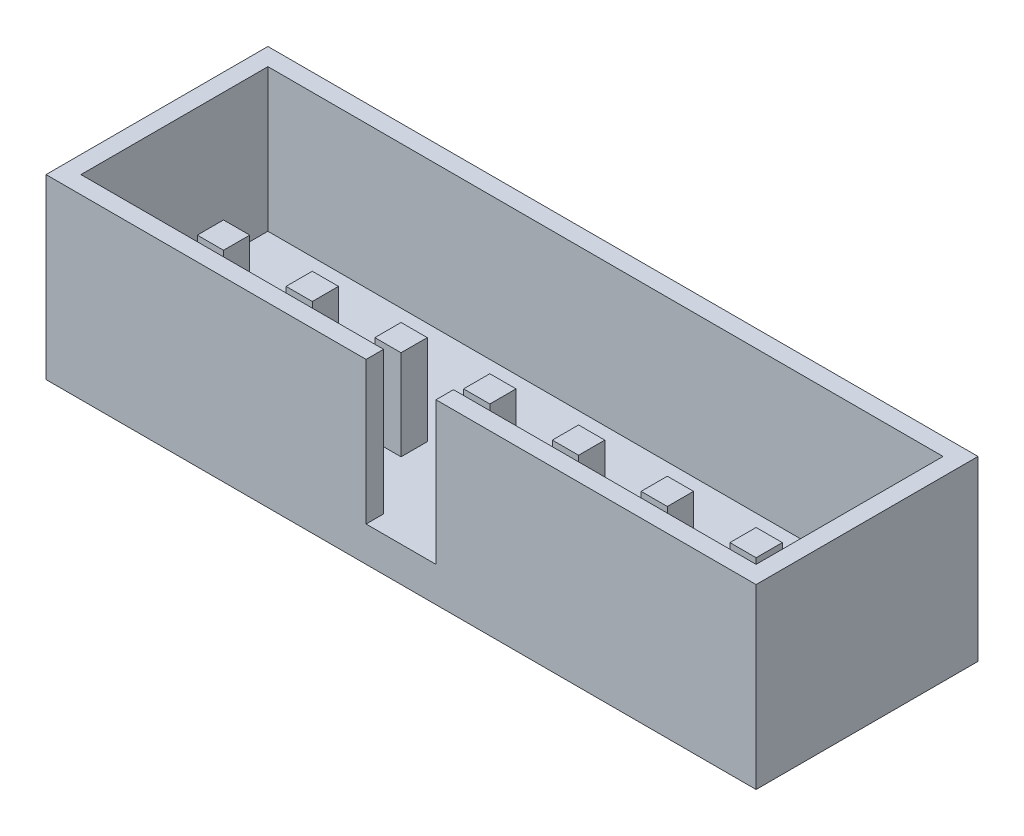
SolidWorks part; units mm, degrees
ref_plane "前视基准面" through (0, 0, 0) normal (0, 0, 1) x (1, 0, 0)
ref_plane "上视基准面" through (0, 0, 0) normal (0, 1, 0) x (1, 0, 0)
ref_plane "右视基准面" through (0, 0, 0) normal (1, 0, 0) x (0, 0, -1)
sketch "草图1" plane through (0, 0, 0) normal (0, 1, 0) x (1, 0, 0)
  line L0 (0, 7.1914) -> (0, -5.4429) construction
  line L1 (-10.16, 3.175) -> (10.16, 3.175)
  line L2 (-10.16, 3.175) -> (-10.16, -3.175)
  line L3 (-10.16, -3.175) -> (10.16, -3.175)
  line L4 (10.16, 3.175) -> (10.16, -3.175)
  line L5 (-10.6234, 0) -> (16.1963, 0) construction
  dimension "D1" = 20.32
  dimension "D2" = 6.35
extrude "拉伸1" add sketch "草图1" along normal blind 5.08
sketch "草图2" plane through (0, 5.08, 0) normal (0, 1, 0) x (-1, 0, 0)
  line L8 (9.66, -2.675) -> (9.66, 2.675)
  line L9 (9.66, 2.675) -> (-9.66, 2.675)
  line L10 (-9.66, 2.675) -> (-9.66, -2.675)
  line L11 (-9.66, -2.675) -> (9.66, -2.675)
  line L12 (9.66, -2.675) -> (9.66, 2.675)
  line L13 (9.66, 2.675) -> (-9.66, 2.675)
  line L14 (-9.66, 2.675) -> (-9.66, -2.675)
  line L15 (-9.66, -2.675) -> (9.66, -2.675)
  dimension "D1" = 0.5
extrude "切除-拉伸1" cut sketch "草图2" against normal offset from surface (4.08 mm away) 1 up to face at (0, 0, 0)
sketch "草图3" plane through (0, 0, 3.175) normal (0, 0, 1) x (1, 0, 0)
  line L0 (-10.16, 5.08) -> (10.16, 5.08) construction
  line L1 (-1, 5.08) -> (1, 5.08)
  line L2 (-1, 5.08) -> (-1, 1)
  line L3 (-1, 1) -> (1, 1)
  line L4 (1, 5.08) -> (1, 1)
  line L5 (9.66, 1) -> (-9.66, 1) construction
  line L6 (0, -1.5083) -> (0, 12.2426) construction
  dimension "D1" = 2
extrude "切除-拉伸2" cut sketch "草图3" against normal blind 1
sketch "草图4" plane through (0, 0, 0) normal (0, -1, 0) x (1, 0, 0)
  line L0 (7.6775, 0.635) -> (-8.5467, 0.635) construction
  line L1 (4.705, 1.01) -> (5.455, 1.01)
  line L2 (0, -3.6953) -> (0, 4.0669) construction
  line L3 (0, 2.1009) -> (0, -0.7012) construction
  line L4 (-0.375, 1.01) -> (0.375, 1.01)
  line L5 (-0.375, 1.01) -> (-0.375, 0.26)
  line L6 (-0.375, 0.26) -> (0.375, 0.26)
  line L7 (0.375, 1.01) -> (0.375, 0.26)
  line L8 (2.165, 1.01) -> (2.915, 1.01)
  line L9 (2.165, 1.01) -> (2.165, 0.26)
  line L10 (2.165, 0.26) -> (2.915, 0.26)
  line L11 (2.915, 1.01) -> (2.915, 0.26)
  line L12 (4.705, 1.01) -> (4.705, 0.26)
  line L13 (4.705, 0.26) -> (5.455, 0.26)
  line L14 (5.455, 1.01) -> (5.455, 0.26)
  line L15 (7.245, 1.01) -> (7.995, 1.01)
  line L16 (-2.915, 1.01) -> (-2.165, 1.01)
  line L17 (-2.915, 1.01) -> (-2.915, 0.26)
  line L18 (-2.915, 0.26) -> (-2.165, 0.26)
  line L19 (-2.165, 1.01) -> (-2.165, 0.26)
  line L20 (4.705, 1.01) -> (5.455, 1.01) [skipped]
  line L21 (4.705, 1.01) -> (4.705, 0.26) [skipped]
  line L22 (4.705, 0.26) -> (5.455, 0.26) [skipped]
  line L23 (5.455, 1.01) -> (5.455, 0.26) [skipped]
  line L24 (7.245, 1.01) -> (7.245, 0.26)
  line L25 (7.245, 0.26) -> (7.995, 0.26)
  line L26 (7.995, 1.01) -> (7.995, 0.26)
  line L27 (-7.995, 1.01) -> (-7.995, 0.26)
  line L28 (-7.245, 0.26) -> (-7.995, 0.26)
  line L29 (-7.245, 1.01) -> (-7.245, 0.26)
  line L30 (-7.245, 1.01) -> (-7.995, 1.01)
  line L31 (-5.455, 1.01) -> (-5.455, 0.26)
  line L32 (-4.705, 0.26) -> (-5.455, 0.26)
  line L33 (-4.705, 1.01) -> (-4.705, 0.26)
  line L34 (-4.705, 1.01) -> (-5.455, 1.01)
  dimension "D1" = 3
  dimension "D2" = 0.75
  dimension "D3" = 0.75
  dimension "D4" = 0
extrude "拉伸2" add sketch "草图4" along normal blind 2 and the other way offset from surface 1.5 other way up to face at (0, 5.08, 0.975)
